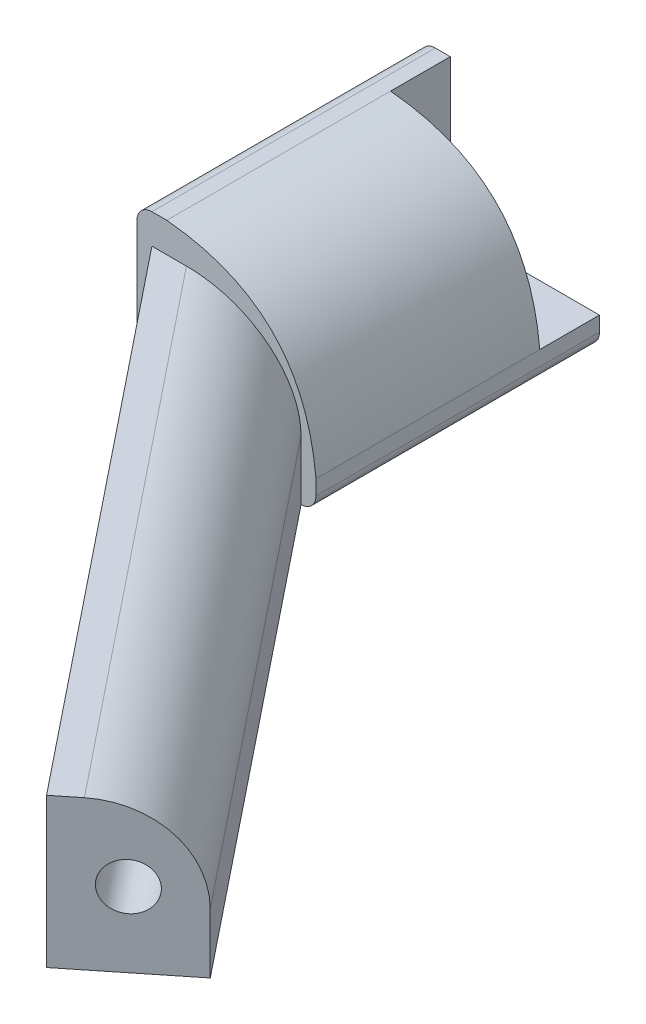
SolidWorks part; units mm, degrees
ref_plane "Front Plane" through (0, 0, 0) normal (0, 0, 1) x (1, 0, 0)
ref_plane "Top Plane" through (0, 0, 0) normal (0, 1, 0) x (1, 0, 0)
ref_plane "Right Plane" through (0, 0, 0) normal (1, 0, 0) x (0, 0, -1)
sketch "Sketch1" plane through (0, 0, 0) normal (0, 0, 1) x (1, 0, 0)
  line L0 (0, 0) -> (12.7, 0)
  line L1 (0, 0) -> (0, 12.7)
  circle A0 centre (5.08, 5.08) radius 3.1115
  spline S0 degree 2 poles (0, 12.7) (11.6203, 11.6203) (12.7, 0) knots 0 0 0 1 1 1
  dimension "D5" = 6.223
  dimension "D1" = 12.7
  dimension "D2" = 12.7
  dimension "D3" = 5.08
  dimension "D4" = 5.08
extrude "Boss-Extrude1" add sketch "Sketch1" along normal blind 3.81
sketch "Sketch2" plane through (0, 0, 0) normal (0, 0, -1) x (-1, 0, 0)
  line L0 (0, 12.7) -> (1.27, 12.7)
  line L1 (2.54, 11.43) -> (2.54, -1.27)
  line L2 (0, 12.7) -> (0, 0) construction
  line L3 (-12.7, 0) -> (-12.7, -1.27)
  line L4 (-11.43, -2.54) -> (1.27, -2.54)
  line L5 (0, 12.7) -> (0, 0)
  line L6 (0, 0) -> (-12.7, 0)
  arc A0 (1.27, 12.7) -> (2.54, 11.43) centre (1.27, 11.43) cw
  arc A1 (-12.7, -1.27) -> (-11.43, -2.54) centre (-11.43, -1.27) ccw
  arc A2 (1.27, -2.54) -> (2.54, -1.27) centre (1.27, -1.27) ccw
  point P14 (-12.7, -2.54)
  dimension "D3" = 1.27
  dimension "D1" = 2.54
  dimension "D2" = 2.54
extrude "Boss-Extrude2" add sketch "Sketch2" along normal blind 5.08 and the other way blind 3.81 contours L1 A2 L4 A1 L3 L6 L5 L0 A0
sketch "Sketch3" plane through (0, 0, 3.81) normal (0, 0, 1) x (1, 0, 0)
  line L0 (-2.54, 11.43) -> (-2.54, -1.27)
  line L1 (-1.27, -2.54) -> (11.43, -2.54)
  line L2 (12.7, -1.27) -> (12.7, 0)
  line L3 (-1.27, 12.7) -> (0, 12.7)
  arc A0 (11.43, -2.54) -> (12.7, -1.27) centre (11.43, -1.27) ccw
  arc A1 (-2.54, 11.43) -> (-1.27, 12.7) centre (-1.27, 11.43) cw
  circle A2 centre (5.08, 5.08) radius 1.2
  arc A3 (-2.54, -1.27) -> (-1.27, -2.54) centre (-1.27, -1.27) ccw
  spline S0 degree 2 poles (0, 12.7) (11.6203, 11.6203) (12.7, 0) knots 0 0 0 1 1 1
  dimension "D1" = 1.27
  dimension "D2" = 2.4
  dimension "D3" = 1.27
extrude "Boss-Extrude3" add sketch "Sketch3" along normal blind 2.54
sketch "Sketch4" plane through (0, 0, 6.35) normal (0, 0, 1) x (1, 0, 0)
  line L0 (-2.54, 11.43) -> (-2.54, -1.27)
  line L1 (-1.27, -2.54) -> (11.43, -2.54)
  line L2 (12.7, -1.27) -> (12.7, 0)
  line L3 (-1.27, 12.7) -> (0, 12.7)
  arc A0 (11.43, -2.54) -> (12.7, -1.27) centre (11.43, -1.27) ccw
  arc A1 (-2.54, 11.43) -> (-1.27, 12.7) centre (-1.27, 11.43) cw
  circle A2 centre (5.08, 5.08) radius 3.175
  arc A3 (-2.54, -1.27) -> (-1.27, -2.54) centre (-1.27, -1.27) ccw
  spline S0 degree 2 poles (0, 12.7) (11.6203, 11.6203) (12.7, 0) knots 0 0 0 1 1 1
  dimension "D1" = 1.27
  dimension "D2" = 6.35
  dimension "D3" = 1.27
extrude "Boss-Extrude4" add sketch "Sketch4" along normal blind 12.7
sketch "Sketch5" plane through (0, -2.54, 0) normal (0, -1, 0) x (1, 0, 0)
  line L0 (11.43, 19.05) -> (11.43, -5.08) construction
  line L1 (-1.27, 19.05) -> (34.7245, 64.0107)
  line L2 (11.43, 19.05) -> (42.4641, 57.8146)
  line L3 (-1.27, 19.05) -> (-1.27, -5.08) construction
  line L4 (42.4641, 57.8146) -> (34.7245, 64.0107)
  line L5 (11.43, 19.05) -> (-1.27, 19.05)
  dimension "D1" = 141.32
  dimension "D2" = 141.32
  dimension "D3" = 57.594
extrude "Boss-Extrude5" add sketch "Sketch5" against normal blind 12.7 contours L2 L4 L1 L5
sketch "Sketch7" plane through (0, 0, 19.05) normal (0, 0, 1) x (1, 0, 0)
  circle A0 centre (5.08, 5.08) radius 3.1115
extrude "Cut-Extrude1" cut sketch "Sketch7" along normal through all
sketch "Sketch8" plane through (44.7926, 0, 55.9504) normal (0.625, 0, 0.7806) x (0.7806, 0, -0.625)
  circle A0 centre (-7.94, 3.81) radius 2
  dimension "D1" = 4
extrude "Cut-Extrude2" cut sketch "Sketch8" against normal blind 7
fillet "Fillet1" radius 7.62 1 edges at (26.947, 10.16, 38.4323)
